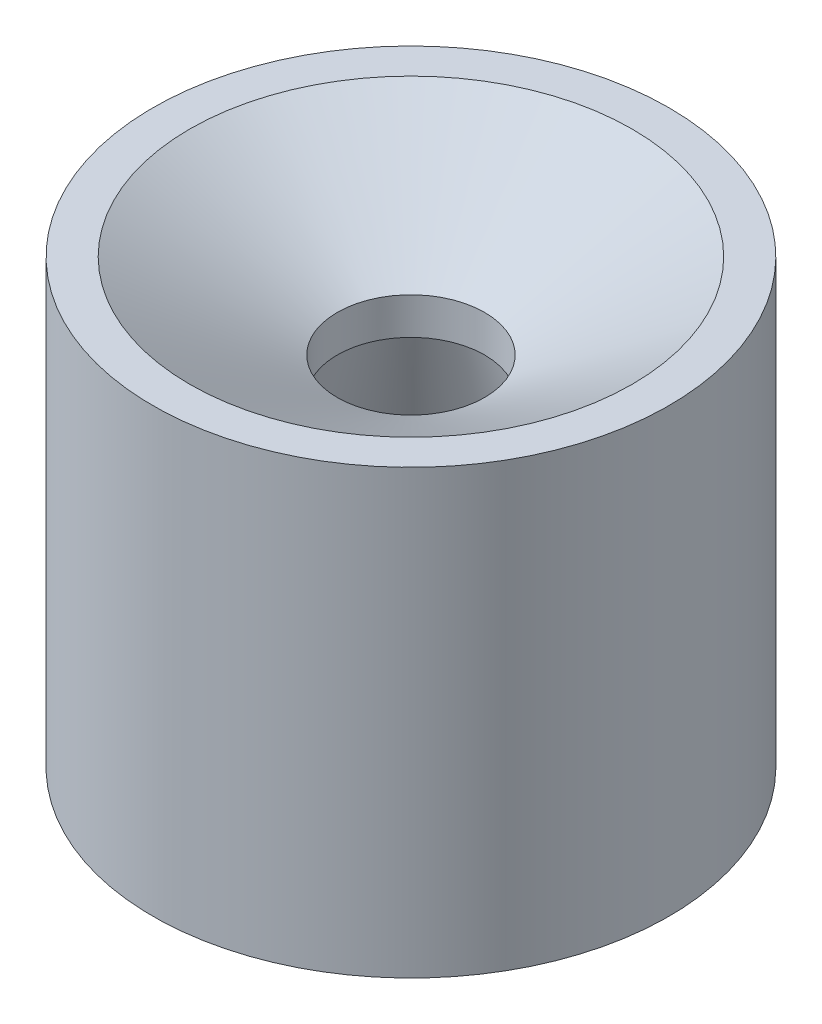
SolidWorks part; units mm, degrees
material "C (Graphite)"
ref_plane "Front Plane" through (0, 0, 0) normal (0, 0, 1) x (1, 0, 0)
ref_plane "Top Plane" through (0, 0, 0) normal (0, 1, 0) x (1, 0, 0)
ref_plane "Right Plane" through (0, 0, 0) normal (1, 0, 0) x (0, 0, -1)
sketch "Sketch1" plane through (0, 0, 0) normal (0, 0, 1) x (1, 0, 0)
  line L0 (0, 0) -> (0, 76.2) construction
  line L1 (0, 0) -> (-44.45, 0) construction
  line L2 (-44.45, 0) -> (-44.45, 76.2)
  line L4 (-12.7, 61.5353) -> (-12.7, 55.1853)
  line L5 (-12.7, 55.1853) -> (-28.321, 0)
  line L6 (-28.321, 0) -> (-44.45, 0)
  line L7 (-44.45, 76.2) -> (-38.1, 76.2)
  line L8 (-38.1, 76.2) -> (-12.7, 61.5353)
  dimension "D1" = 76.2
  dimension "D2" = 28.321
  dimension "D3" = 12.7
  dimension "D4" = 6.35
  dimension "D5" = 44.45
  dimension "D6" = 6.35
  dimension "D7" = 30
  dimension "D8" = 16.129
revolve "Revolve1" add sketch "Sketch1" angle 360 about L0
